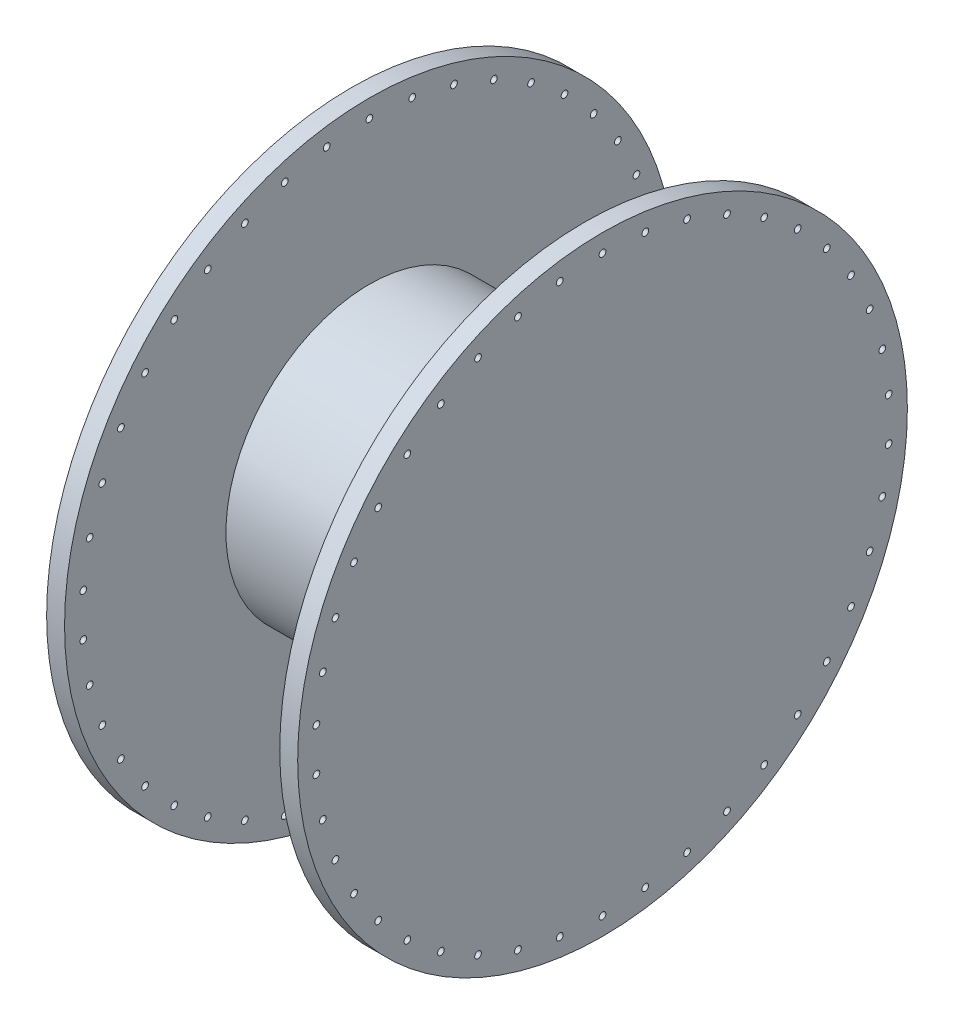
SolidWorks part; units mm, degrees
ref_plane "Front Plane" through (0, 0, 0) normal (0, 0, 1) x (1, 0, 0)
ref_plane "Top Plane" through (0, 0, 0) normal (0, 1, 0) x (1, 0, 0)
ref_plane "Right Plane" through (0, 0, 0) normal (1, 0, 0) x (0, 0, -1)
ref_axis "Axis1" through (-24.4475, 0, 0) along (1, 0, 0)
sketch "Sketch1" plane through (0, 0, 0) normal (1, 0, 0) x (0, 0, -1)
  line L0 (0, 53.975) -> (0, -53.975) construction
  line L1 (53.975, 0) -> (-53.975, 0) construction
  circle A0 centre (0, 0) radius 25.4
  circle A1 centre (0, 0) radius 53.975
  circle A2 centre (0, 50.8) radius 0.5953
  circle A3 centre (7.5713, 50.2326) radius 0.5953
  circle A4 centre (14.9736, 48.5431) radius 0.5953
  circle A5 centre (22.0413, 45.7692) radius 0.5953
  circle A6 centre (28.6167, 41.9729) radius 0.5953
  circle A7 centre (34.5528, 37.239) radius 0.5953
  circle A8 centre (39.717, 31.6733) radius 0.5953
  circle A9 centre (43.9941, 25.4) radius 0.5953
  circle A10 centre (47.2884, 18.5593) radius 0.5953
  circle A11 centre (49.5263, 11.3041) radius 0.5953
  circle A12 centre (50.658, 3.7963) radius 0.5953
  circle A13 centre (50.658, -3.7963) radius 0.5953
  circle A14 centre (49.5263, -11.3041) radius 0.5953
  circle A15 centre (47.2884, -18.5593) radius 0.5953
  circle A16 centre (43.9941, -25.4) radius 0.5953
  circle A17 centre (39.717, -31.6733) radius 0.5953
  circle A18 centre (34.5528, -37.239) radius 0.5953
  circle A19 centre (28.6167, -41.9729) radius 0.5953
  circle A20 centre (22.0413, -45.7692) radius 0.5953
  circle A21 centre (14.9736, -48.5431) radius 0.5953
  circle A22 centre (7.5713, -50.2326) radius 0.5953
  circle A23 centre (0, -50.8) radius 0.5953
  circle A24 centre (-7.5713, -50.2326) radius 0.5953
  circle A25 centre (-14.9736, -48.5431) radius 0.5953
  circle A26 centre (-22.0413, -45.7692) radius 0.5953
  circle A27 centre (-28.6167, -41.9729) radius 0.5953
  circle A28 centre (-34.5528, -37.239) radius 0.5953
  circle A29 centre (-39.717, -31.6733) radius 0.5953
  circle A30 centre (-43.9941, -25.4) radius 0.5953
  circle A31 centre (-47.2884, -18.5593) radius 0.5953
  circle A32 centre (-49.5263, -11.3041) radius 0.5953
  circle A33 centre (-50.658, -3.7963) radius 0.5953
  circle A34 centre (-50.658, 3.7963) radius 0.5953
  circle A35 centre (-49.5263, 11.3041) radius 0.5953
  circle A36 centre (-47.2884, 18.5593) radius 0.5953
  circle A37 centre (-43.9941, 25.4) radius 0.5953
  circle A38 centre (-39.717, 31.6733) radius 0.5953
  circle A39 centre (-34.5528, 37.239) radius 0.5953
  circle A40 centre (-28.6167, 41.9729) radius 0.5953
  circle A41 centre (-22.0413, 45.7692) radius 0.5953
  circle A42 centre (-14.9736, 48.5431) radius 0.5953
  circle A43 centre (-7.5713, 50.2326) radius 0.5953
  point P102 (0, 0)
  point P109 (0, 0)
  point P110 (0, 0)
  dimension "D1" = 1.1906
  dimension "D2" = 107.95
  dimension "D3" = 50.8
  dimension "D4" = 50.8
  dimension "D5" = 42
extrude "Boss-Extrude1" add sketch "Sketch1" along normal mid plane 44.45 contours A0
extrude "Boss-Extrude2" add sketch "Sketch1<3>" against normal blind 3.175 from surface contours A1 A0 region at (0, 0, 52.4484) starting at face at (22.225, 0, -25.4)
sketch "Sketch1<3>" plane through (0, 0, 0) normal (1, 0, 0) x (0, 0, -1) same geometry as "Sketch1"
extrude "Boss-Extrude3" add sketch "Sketch1<4>" along normal blind 3.175 from surface starting at face at (-22.225, 0, -25.4)
sketch "Sketch1<4>" plane through (0, 0, 0) normal (1, 0, 0) x (0, 0, -1) same geometry as "Sketch1"
